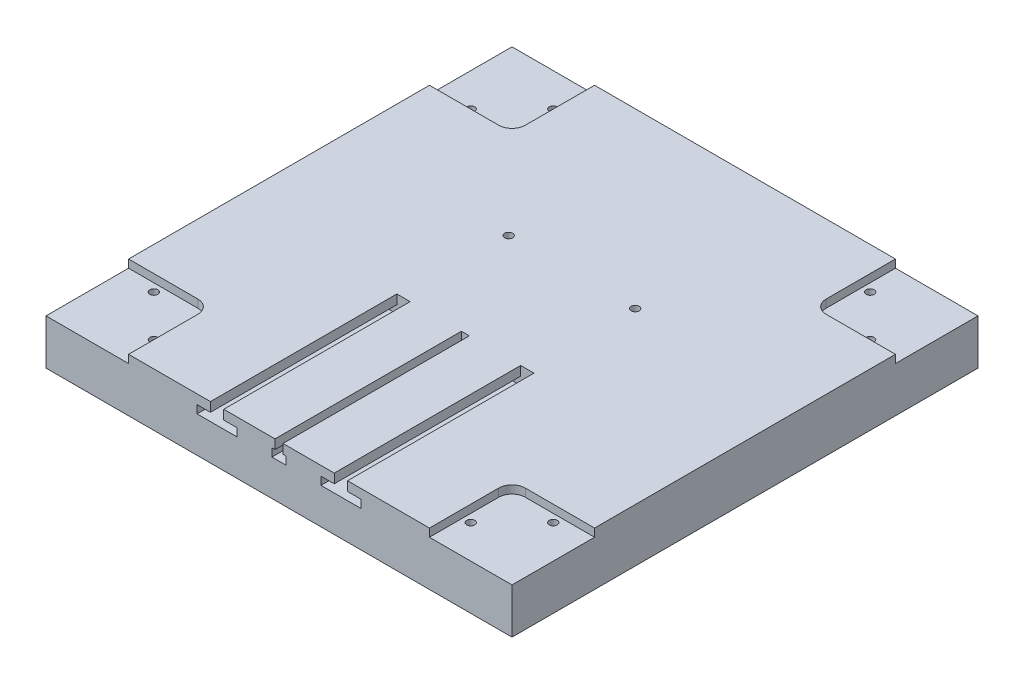
SolidWorks part; units mm, degrees
ref_plane "Front Plane" through (0, 0, 0) normal (0, 0, 1) x (1, 0, 0)
ref_plane "Top Plane" through (0, 0, 0) normal (0, 1, 0) x (1, 0, 0)
ref_plane "Right Plane" through (0, 0, 0) normal (1, 0, 0) x (0, 0, -1)
sketch "Sketch1" plane through (0, 0, 0) normal (0, 1, 0) x (1, 0, 0)
  line L0 (0, 87.5) -> (0, -87.5) construction
  line L1 (-87.5, 87.5) -> (87.5, 87.5)
  line L2 (-87.5, 87.5) -> (-87.5, -87.5)
  line L3 (-87.5, -87.5) -> (87.5, -87.5)
  line L4 (87.5, 87.5) -> (87.5, -87.5)
  line L5 (-87.5, 87.5) -> (87.5, -87.5) construction
  line L6 (-87.5, -87.5) -> (87.5, 87.5) construction
  line L15 (-87.5, 0) -> (87.5, 0) construction
  point P0 (0, 0)
  dimension "D1" = 175
  dimension "D2" = 175
extrude "Boss-Extrude2" add sketch "Sketch1" along normal blind 20
sketch "Sketch7" plane through (0, 20, 0) normal (0, 1, 0) x (1, 0, 0)
  line L0 (0, 87.5) -> (0, -87.5) construction
  line L1 (-87.5, 87.5) -> (-56.5, 87.5)
  line L2 (-87.5, 87.5) -> (-87.5, 56.5)
  line L3 (-87.5, 56.5) -> (-61.5, 56.5)
  line L4 (-56.5, 87.5) -> (-56.5, 61.5)
  line L5 (87.5, 87.5) -> (-87.5, 87.5) construction
  line L6 (-87.5, -87.5) -> (87.5, -87.5) construction
  line L7 (-87.5, 0) -> (87.5, 0) construction
  line L8 (-87.5, 87.5) -> (-87.5, -87.5) construction
  line L9 (87.5, -87.5) -> (87.5, 87.5) construction
  line L10 (87.5, 56.5) -> (61.5, 56.5)
  line L11 (56.5, 87.5) -> (56.5, 61.5)
  line L12 (87.5, 87.5) -> (56.5, 87.5)
  line L13 (87.5, 87.5) -> (87.5, 56.5)
  line L14 (87.5, -87.5) -> (87.5, -56.5)
  line L15 (87.5, -87.5) -> (56.5, -87.5)
  line L16 (56.5, -87.5) -> (56.5, -61.5)
  line L17 (87.5, -56.5) -> (61.5, -56.5)
  line L18 (-56.5, -87.5) -> (-56.5, -61.5)
  line L19 (-87.5, -56.5) -> (-61.5, -56.5)
  line L20 (-87.5, -87.5) -> (-87.5, -56.5)
  line L21 (-87.5, -87.5) -> (-56.5, -87.5)
  arc A0 (-61.5, 56.5) -> (-56.5, 61.5) centre (-61.5, 61.5) ccw
  arc A1 (61.5, 56.5) -> (56.5, 61.5) centre (61.5, 61.5) cw
  arc A2 (61.5, -56.5) -> (56.5, -61.5) centre (61.5, -61.5) ccw
  arc A3 (-61.5, -56.5) -> (-56.5, -61.5) centre (-61.5, -61.5) cw
  point P7 (-56.5, 56.5)
  point P38 (-56.5, -56.5)
  dimension "D3" = 5
  dimension "D1" = 31
  dimension "D2" = 31
extrude "Cut-Extrude6" cut sketch "Sketch7" against normal blind 3
sketch "Sketch8" plane through (0, 17, 0) normal (0, 1, 0) x (1, 0, 0)
  line L0 (-75, -62.5) -> (-75, -56.5) construction
  line L5 (-61.5, -56.5) -> (-87.5, -56.5) construction
  line L6 (-62.5, -75) -> (-56.5, -75) construction
  line L7 (-56.5, -87.5) -> (-56.5, -61.5) construction
  line L8 (-87.5, -87.5) -> (-56.5, -87.5) construction
  line L9 (-87.5, -56.5) -> (-87.5, -87.5) construction
  line L10 (0, 87.5) -> (0, -87.5) construction
  line L11 (56.5, 87.5) -> (-56.5, 87.5) construction
  line L12 (-56.5, -87.5) -> (56.5, -87.5) construction
  line L13 (62.5, -75) -> (56.5, -75) construction
  line L14 (75, -62.5) -> (75, -56.5) construction
  line L15 (-87.5, 0) -> (87.5, 0) construction
  line L16 (-87.5, 56.5) -> (-87.5, -56.5) construction
  line L17 (87.5, -56.5) -> (87.5, 56.5) construction
  circle A0 centre (-75, -59.5) radius 1.5
  circle A1 centre (-59.5, -75) radius 1.5
  circle A2 centre (59.5, -75) radius 1.5
  circle A3 centre (75, -59.5) radius 1.5
  circle A4 centre (59.5, 75) radius 1.5
  circle A5 centre (75, 59.5) radius 1.5
  circle A6 centre (-59.5, 75) radius 1.5
  circle A7 centre (-75, 59.5) radius 1.5
  dimension "D3" = 3
  dimension "D4" = 3
  dimension "D1" = 28
  dimension "D2" = 28
  dimension "D5" = 12.5
  dimension "D6" = 12.5
extrude "Cut-Extrude7" cut sketch "Sketch8" against normal up to next
sketch "Sketch9" plane through (0, 0, 87.5) normal (0, 0, 1) x (1, 0, 0)
  line L0 (0, 20) -> (0, 0) construction
  line L1 (-56.5, 20) -> (56.5, 20) construction
  line L2 (0, 10) -> (-46.5, 10) construction
  line L3 (-46.5, 20) -> (46.5, 20)
  line L4 (-46.5, 20) -> (-46.5, 0)
  line L5 (-46.5, 0) -> (46.5, 0)
  line L6 (46.5, 20) -> (46.5, 0)
  line L7 (-46.5, 20) -> (46.5, 0) construction
  line L8 (-46.5, 0) -> (46.5, 20) construction
  line L9 (-46.5, 10) -> (0, 10) construction
  line L10 (-20.75, 16.5) -> (-15.75, 16.5)
  line L11 (-23.25, 10) -> (-23.25, 20) construction
  line L12 (-30.75, 16.5) -> (-25.75, 16.5)
  line L13 (-30.75, 16.5) -> (-30.75, 13.5)
  line L14 (-30.75, 13.5) -> (-15.75, 13.5)
  line L15 (-15.75, 16.5) -> (-15.75, 13.5)
  line L16 (-30.75, 16.5) -> (-15.75, 13.5) construction
  line L17 (-30.75, 13.5) -> (-15.75, 16.5) construction
  line L18 (-25.75, 20) -> (-20.75, 20)
  line L19 (-25.75, 20) -> (-25.75, 16.5)
  line L21 (-20.75, 20) -> (-20.75, 16.5)
  line L22 (-25.75, 20) -> (-20.75, 16.5) construction
  line L23 (-25.75, 16.5) -> (-20.75, 20) construction
  line L24 (25.75, 16.5) -> (20.75, 20) construction
  line L25 (25.75, 20) -> (20.75, 16.5) construction
  line L26 (30.75, 13.5) -> (15.75, 16.5) construction
  line L27 (30.75, 16.5) -> (15.75, 13.5) construction
  line L28 (20.75, 20) -> (20.75, 16.5)
  line L29 (25.75, 20) -> (25.75, 16.5)
  line L30 (25.75, 20) -> (20.75, 20)
  line L31 (15.75, 16.5) -> (15.75, 13.5)
  line L32 (30.75, 13.5) -> (15.75, 13.5)
  line L33 (30.75, 16.5) -> (30.75, 13.5)
  line L34 (30.75, 16.5) -> (25.75, 16.5)
  line L35 (20.75, 16.5) -> (15.75, 16.5)
  line L36 (-15.75, 15) -> (15.75, 15) construction
  line L37 (1.5, 16.5) -> (2.65, 16.5)
  line L38 (-2.65, 16.5) -> (-1.5, 16.5)
  line L39 (-2.65, 16.5) -> (-2.65, 13.5)
  line L40 (-2.65, 13.5) -> (2.65, 13.5)
  line L41 (2.65, 16.5) -> (2.65, 13.5)
  line L42 (-2.65, 16.5) -> (2.65, 13.5) construction
  line L43 (-2.65, 13.5) -> (2.65, 16.5) construction
  line L44 (-1.5, 20) -> (1.5, 20)
  line L45 (-1.5, 20) -> (-1.5, 16.5)
  line L47 (1.5, 20) -> (1.5, 16.5)
  line L48 (-1.5, 20) -> (1.5, 16.5) construction
  line L49 (-1.5, 16.5) -> (1.5, 20) construction
  point P5 (0, 10)
  point P13 (-23.25, 15)
  point P19 (-23.25, 18.25)
  point P32 (23.25, 18.25)
  point P33 (23.25, 15)
  point P36 (0, 15)
  point P41 (0, 18.25)
  dimension "D1" = 93
  dimension "D2" = 20
  dimension "D3" = 3
  dimension "D4" = 15
  dimension "D5" = 3.5
  dimension "D6" = 5
  dimension "D7" = 5.3
  dimension "D8" = 3
  dimension "D9" = 3.5
  dimension "D10" = 3
extrude "Cut-Extrude8" cut sketch "Sketch9" against normal blind 70 contours L21 L3 L19 L12 L13 L14 L15 L10 | L28 L35 L31 L32 L33 L34 L29 L3 | L38 L45 L44 L47 L37 L41 L40 L39 region at (-23.25, 15.91, 87.5) region at (23.25, 15.91, 87.5)
sketch "Sketch10" plane through (0, 20, 0) normal (0, 1, 0) x (1, 0, 0)
  line L0 (56.5, 87.5) -> (-56.5, 87.5) construction
  line L1 (-23.75, 22.5) -> (23.75, 22.5) construction
  line L3 (87.5, -56.5) -> (87.5, 56.5) construction
  circle A0 centre (-23.75, 22.5) radius 1.5
  circle A1 centre (23.75, 22.5) radius 1.5
  point P2 (0, 87.5)
  point P3 (0, 22.5)
  point P7 (0, 32.5)
  dimension "D1" = 3
  dimension "D2" = 3
  dimension "D3" = 47.5
  dimension "D4" = 55
  dimension "D5" = 87.5
extrude "Cut-Extrude9" cut sketch "Sketch10" against normal up to next
